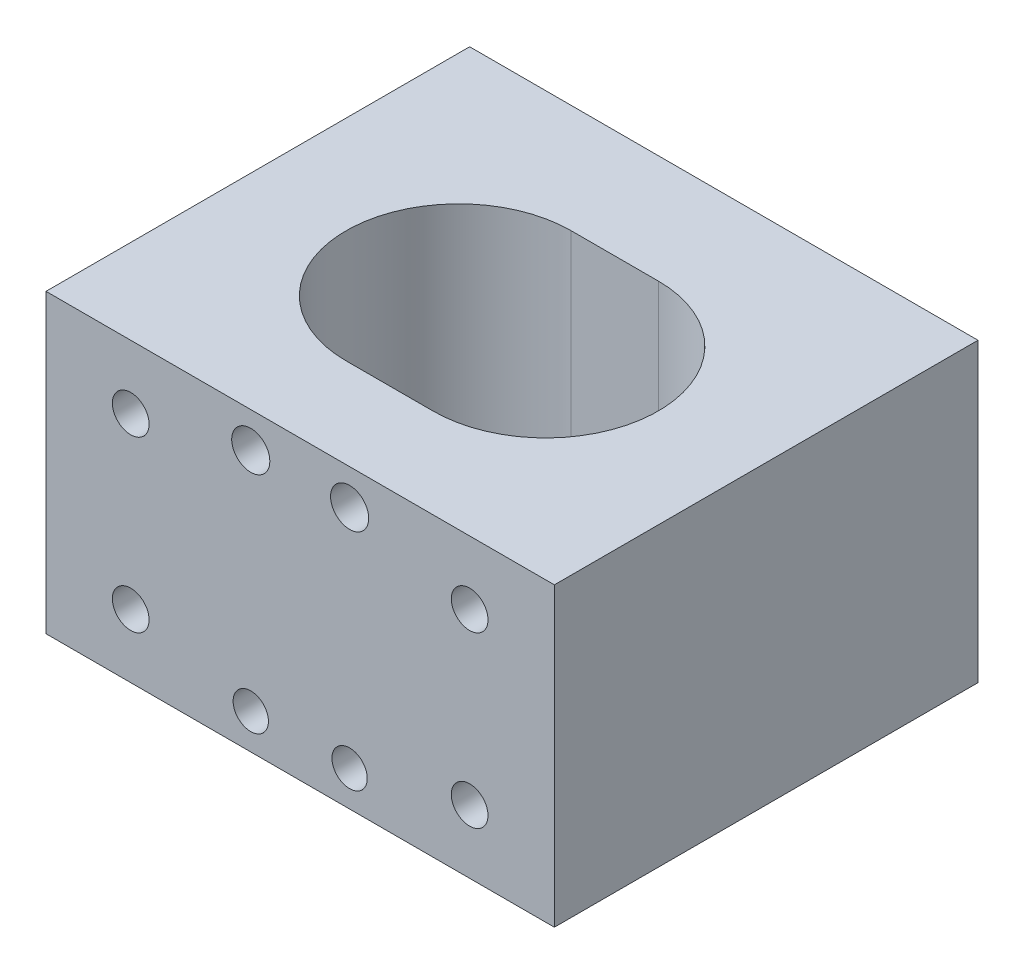
SolidWorks part; units mm, degrees
ref_plane "정면" through (0, 0, 0) normal (0, 0, 1) x (1, 0, 0)
ref_plane "윗면" through (0, 0, 0) normal (0, 1, 0) x (1, 0, 0)
ref_plane "우측면" through (0, 0, 0) normal (1, 0, 0) x (0, 0, -1)
sketch "스케치1" plane through (0, 0, 0) normal (0, 0, 1) x (1, 0, 0)
  line L0 (0, 10.5) -> (0, -10.5) construction
  line L1 (18, -10.5) -> (-18, -10.5)
  line L2 (18, -10.5) -> (18, 10.5)
  line L3 (18, 10.5) -> (-18, 10.5)
  line L4 (-18, -10.5) -> (-18, 10.5)
  line L5 (18, -10.5) -> (-18, 10.5) construction
  line L6 (18, 10.5) -> (-18, -10.5) construction
  line L7 (18, 0) -> (-18, 0) construction
  circle A0 centre (12, 6) radius 1.3
  circle A1 centre (-12, 6) radius 1.3
  circle A2 centre (12, -6) radius 1.3
  circle A3 centre (-12, -6) radius 1.3
  circle A4 centre (3.5, -8) radius 1.25
  circle A5 centre (-3.5, -8) radius 1.25
  circle A6 centre (3.5, 8) radius 1.35
  circle A7 centre (-3.5, 8) radius 1.35
  point P1 (0, 0)
extrude "보스-돌출1" add sketch "스케치1" along normal blind 30 contours A0 | A6 | A7 | A1 | A3 | A5 | A4 | A2 | L4 L1 L2 L3 A5 A4 A1 A0 A2 A3 A6 A7 region at (0, -0.0183, 0) region at (12, 6, 0) region at (-12, 6, 0) region at (12, -6, 0) region at (-12, -6, 0) region at (3.5, -8, 0) region at (-3.5, -8, 0) region at (3.5, 8, 0) region at (-3.5, 8, 0)
extrude "컷-돌출1" cut sketch "스케치1<5>" along normal blind 4 contours A0 | A6 | A7 | A1 | A3 | A5 | A4 | A2 region at (12, 6, 0) region at (-12, 6, 0) region at (-12, -6, 0) region at (3.5, 8, 0) region at (-3.5, 8, 0)
sketch "스케치1<5>" plane through (0, 0, 0) normal (0, 0, 1) x (1, 0, 0) same geometry as "스케치1"
extrude "컷-돌출2" cut sketch "스케치1<6>" against normal blind 4 from surface contours A6 | A0 | A7 | A1 | A3 | A5 | A4 | A2 region at (12, 6, 0) region at (-12, 6, 0) region at (12, -6, 0) region at (-12, -6, 0) region at (3.5, -8, 0) region at (-3.5, -8, 0) region at (3.5, 8, 0) region at (-3.5, 8, 0) starting at face at (0, 0, 30)
sketch "스케치1<6>" plane through (0, 0, 0) normal (0, 0, 1) x (1, 0, 0) same geometry as "스케치1"
sketch "Sketch1" plane through (0, 10.5, 0) normal (0, 1, 0) x (1, 0, 0)
  line L0 (-3.118, -15.6627) -> (3.0447, -15.6627) construction
  line L1 (-3.118, -7.6874) -> (3.0447, -7.6874)
  line L2 (-3.118, -23.638) -> (3.0447, -23.638)
  arc A0 (-3.118, -7.6874) -> (-3.118, -23.638) centre (-3.118, -15.6627) ccw
  arc A1 (3.0447, -23.638) -> (3.0447, -7.6874) centre (3.0447, -15.6627) ccw
  point P2 (-0.0367, -15.6627)
extrude "Cut-Extrude1" cut sketch "Sketch1" against normal blind 30 contours L2 A1 L1 A0
